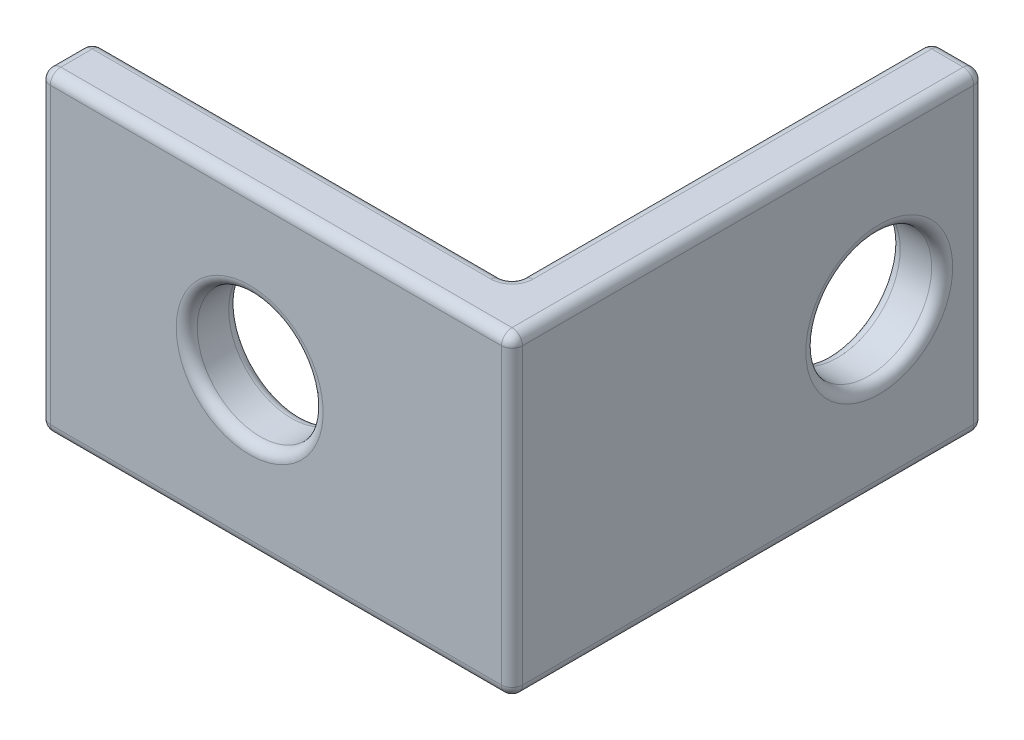
SolidWorks part; units mm, degrees
ref_plane "Front Plane" through (0, 0, 0) normal (0, 0, 1) x (1, 0, 0)
ref_plane "Top Plane" through (0, 0, 0) normal (0, 1, 0) x (1, 0, 0)
ref_plane "Right Plane" through (0, 0, 0) normal (1, 0, 0) x (0, 0, -1)
sketch "Sketch3" plane through (0, 0, 0) normal (0, 1, 0) x (1, 0, 0)
  line L0 (0, 0) -> (22.5, 0)
  line L1 (22.5, 0) -> (22.5, 22.5)
  line L2 (22.5, 22.5) -> (20, 22.5)
  line L3 (20, 22.5) -> (20, 2.5)
  line L4 (20, 2.5) -> (0, 2.5)
  line L5 (0, 2.5) -> (0, 0)
  dimension "D1" = 2.5
  dimension "D2" = 20
extrude "Boss-Extrude2" add sketch "Sketch3" along normal blind 15
sketch "Sketch4" plane through (0, 0, -2.5) normal (0, 0, -1) x (-1, 0, 0)
  line L0 (-20, 15) -> (0, 0) construction
  circle A0 centre (-10, 7.5) radius 3
  dimension "D1" = 6
extrude "Cut-Extrude2" cut sketch "Sketch4" against normal through all
sketch "Sketch7" plane through (20, 0, 0) normal (-1, 0, 0) x (0, 0, 1)
  line L0 (-22.5, 15) -> (-22.5, 0) construction
  line L1 (-22.5, 0) -> (-17.5, 7.5) construction
  line L2 (-17.5, 7.5) -> (-22.5, 15) construction
  circle A1 centre (-17.5, 7.5) radius 3
  dimension "D2" = 6
  dimension "D1" = 5
extrude "Cut-Extrude4" cut sketch "Sketch7" against normal through all
fillet "Fillet1" radius 0.5 22 edges at (22.5, 7.5, 0) (22.5, 15, -11.25) (11.25, 15, 0) (11.25, 0, 0) (22.5, 0, -11.25) (0, 15, -1.25) (0, 7.5, 0) (0, 0, -1.25) (22.5, 7.5, -22.5) (21.25, 15, -22.5) (21.25, 0, -22.5) (10, 15, -2.5) (0, 7.5, -2.5) (10, 0, -2.5) (7, 7.5, -2.5) (20, 7.5, -22.5) (20, 15, -12.5) (20, 7.5, -2.5) (20, 0, -12.5) (20, 7.5, -14.5) (7, 7.5, 0) (22.5, 7.5, -14.5)
equation "\"pulleybolt\"=0.6"
equation "\"D2@Sketch7\"=\"pulleybolt\""
